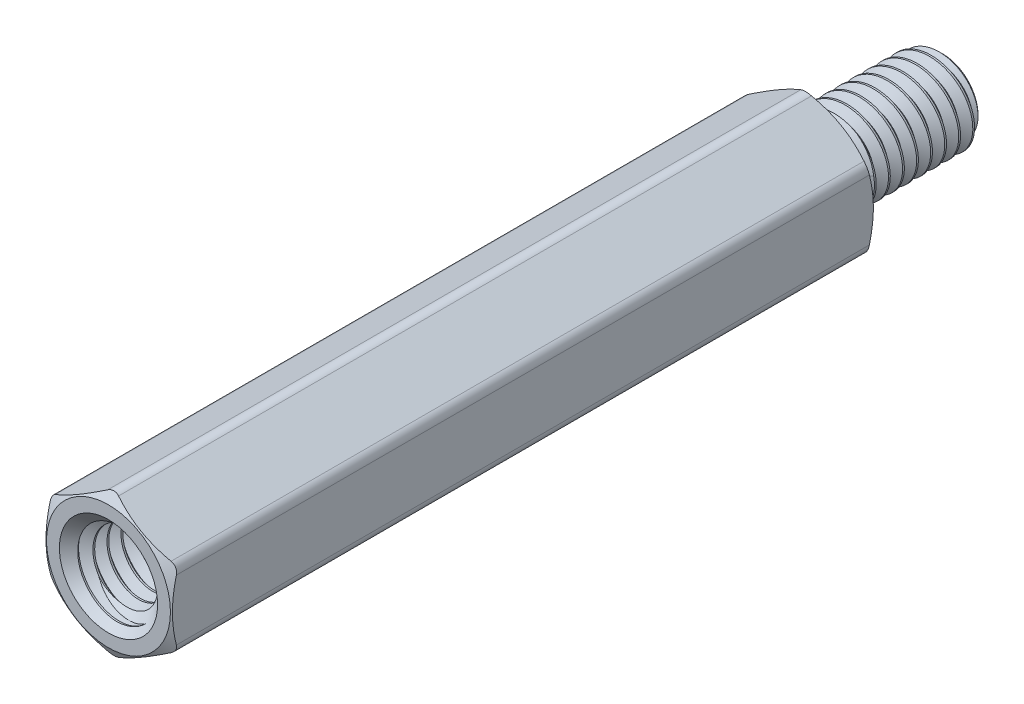
SolidWorks part; units mm, degrees
ref_plane "Front Plane" through (0, 0, 0) normal (0, 0, 1) x (1, 0, 0)
ref_plane "Top Plane" through (0, 0, 0) normal (0, 1, 0) x (1, 0, 0)
ref_plane "Right Plane" through (0, 0, 0) normal (1, 0, 0) x (0, 0, -1)
sketch "Sketch1" plane through (0, 0, 0) normal (0, 0, 1) x (1, 0, 0)
  line L1 (2.25, 1.299) -> (0, 2.5981)
  line L2 (0, 2.5981) -> (-2.25, 1.299)
  line L3 (-2.25, 1.299) -> (-2.25, -1.299)
  line L4 (-2.25, -1.299) -> (0, -2.5981)
  line L5 (0, -2.5981) -> (2.25, -1.299)
  line L6 (2.25, -1.299) -> (2.25, 1.299)
  circle A0 centre (0, 0) radius 2.25 construction
  point P10 (0, -2.25)
  dimension "Hex Size" = 4.5
sketch "Sketch2" plane through (0, 0, 0) normal (1, 0, 0) x (0, 0, -1)
  line L0 (4.7, 0) -> (-25, 0) construction
  line L2 (0, 1.5) -> (0, -1.5) construction
  line L3 (-18.6, 1.5) -> (-18.6, -1.5) construction
  line L4 (-25.4688, 1.5541) -> (-25.2188, 1.1211) construction
  line L5 (-25.2188, 1.1211) -> (-24.9688, 1.5541) construction
  line L6 (-24.9688, 1.5541) -> (-25.4688, 1.5541) construction
  line L7 (-25.4375, 1.5) -> (-25, 1.5) construction
  line L8 (-25.25, 1.1752) -> (-25.1875, 1.1752) construction
  line L9 (-25.2188, 1.1752) -> (-25.2188, 1.1211) construction
  line L10 (-25.2188, 1.5) -> (-25.2188, 1.5541) construction
  line L11 (4.6688, 1.5541) -> (5.1688, 1.5541) construction
  line L12 (5.1688, 1.5541) -> (4.9188, 1.1211) construction
  line L13 (4.9188, 1.1211) -> (4.6688, 1.5541) construction
  line L14 (4.7, 1.5) -> (5.1375, 1.5) construction
  line L15 (4.8875, 1.1752) -> (4.95, 1.1752) construction
  line L16 (4.9188, 1.1752) -> (4.9188, 1.1211) construction
  line L17 (4.9188, 1.5) -> (4.9188, 1.5541) construction
  line L18 (0, 2.5981) -> (-25, 2.5981) construction
  point P6 (0, 0)
  point P9 (-18.6, 0)
  dimension "Length" = 25
sketch "Sketch3" plane through (0, 0, 0) normal (1, 0, 0) x (0, 0, -1)
  line L0 (-18.6, 0) -> (4.7, 0)
  line L1 (-18.6, 1.5) -> (-18.6, -1.5) construction
  line L2 (4.7, 0) -> (4.7, 1.25)
  line L3 (4.7, 1.25) -> (4.45, 1.5)
  line L4 (4.45, 1.5) -> (0.7515, 1.5)
  line L5 (0.7515, 1.5) -> (0.564, 1.1752)
  line L6 (-18.6, 0) -> (-18.6, 1.25)
  line L7 (-18.6, 1.25) -> (-18.85, 1.5)
  line L8 (-18.85, 1.5) -> (-24.75, 1.5)
  line L9 (-24.75, 1.5) -> (-25, 1.75)
  line L10 (4.45, 0) -> (4.45, -1.5) construction
  line L11 (-25, 1.75) -> (-25, 2.25)
  line L12 (-25, 2.25) -> (0, 2.25)
  line L14 (0.564, 1.1752) -> (0.25, 1.1752)
  line L15 (0, 1.4252) -> (0, 2.25)
  arc A0 (0, 1.4252) -> (0.25, 1.1752) centre (0.25, 1.4252) ccw
  point P5 (-25, -2.25)
  point P8 (-23.75, -1.5)
  point P9 (3.45, -1.5)
  point P27 (0, 1.1752)
  dimension "D4" = 0.25
  dimension "D2" = 0.25
  dimension "D1" = 45
  dimension "D6" = 1.25
  dimension "D7" = 60
  dimension "D3" = 1.25
  dimension "D5" = 0.564
revolve "Revolve1" add sketch "Sketch3" angle 360 about L0
sketch "Sketch4" plane through (0, 0, 25) normal (0, 0, 1) x (1, 0, 0)
  line L0 (0, 2.25) -> (0, 1.5) construction
  line L1 (-2.25, 1.299) -> (-2.25, -1.299)
  line L2 (-2.25, -1.299) -> (0, -2.5981)
  line L3 (0, -2.5981) -> (2.25, -1.299)
  line L4 (2.25, -1.299) -> (2.25, 1.299)
  line L5 (2.25, 1.299) -> (0, 2.5981)
  line L6 (0, 2.5981) -> (-2.25, 1.299)
  circle A0 centre (0, 0) radius 2.25 construction
  circle A1 centre (0, 0) radius 1.875
  circle A2 centre (0, 0) radius 2.25 construction
  point P16 (0, 1.875)
extrude "Boss-Extrude1" add sketch "Sketch4" against normal up to surface (25 mm away) up to face at (0, 2.25, 0)
sketch "Sketch5" plane through (0, 0, 25) normal (0, 0, 1) x (1, 0, 0)
  line L0 (-0.8604, 1.2287) -> (0.8604, -1.2287) construction
  line L1 (0, 1.5) -> (0, -1.5) construction
  line L3 (0, -2.7928) -> (0, 2.7928) construction
  circle A0 centre (0, 0) radius 2.205
  point P11 (0.8604, -1.2287)
  dimension "D1" = 4.41
  dimension "D2" = 35
extrude "Cut-Extrude1" cut sketch "Sketch5" against normal through all draft 60 flip side to cut
sketch "Sketch6" plane through (0, 0, 0) normal (0, 0, -1) x (-1, 0, 0)
  circle A0 centre (0, 0) radius 2.205
  circle A1 centre (0, 0) radius 2.205 construction
extrude "Cut-Extrude2" cut sketch "Sketch6" against normal through all draft 60 flip side to cut
fillet "Fillet1" radius 0.3825 6 edges at (0, 2.5981, 12.5) (-2.25, -1.299, 12.5) (0, -2.5981, 12.5) (2.25, -1.299, 12.5) (2.25, 1.299, 12.5) (-2.25, 1.299, 12.5)
sketch "Drawing1" plane through (0, 0, 0) normal (1, 0, 0) x (0, 0, -1)
  line L0 (-25, 1.5) -> (-18.6, 1.5) construction
  line L1 (-18.6, 1.5) -> (-18.6, -1.5) construction
  line L2 (-18.6, -1.5) -> (-25, -1.5) construction
sketch "Sketch7" plane through (0, 0, 0) normal (-1, 0, 0) x (0, 0, 1)
  line L0 (-4.8875, 1.1752) -> (-4.95, 1.1752)
  line L1 (-4.95, 1.1752) -> (-5.1531, 1.5271)
  line L2 (-5.1688, 1.5541) -> (-4.9188, 1.1211) construction
  line L3 (-5.1531, 1.5271) -> (-4.6844, 1.5271)
  line L4 (-4.9188, 1.1211) -> (-4.6688, 1.5541) construction
  line L5 (-4.6844, 1.5271) -> (-4.8875, 1.1752)
  line L6 (-4.9188, 1.5) -> (-4.9188, 1.5541) construction
  point P12 (-4.9188, 1.5271)
sketch "Sketch8" plane through (0, 0, -4.7) normal (0, 0, -1) x (-1, 0, 0)
  circle A0 centre (0, 0) radius 1.5
curve "Helix/Spiral1" pitch 0.5 height 4.559 turns 9.118
sweep "Cut-Sweep1" cut profiles "Sketch7" path "Helix/Spiral1" align with end faces yes
sketch "Sketch9" plane through (0, 0, 18.6) normal (0, 0, 1) x (1, 0, 0)
  circle A0 centre (0, 0) radius 1.75
extrude "Boss-Extrude2" add sketch "Sketch9" along normal up to surface (6.4 mm away) up to face at (0, 1.75, 25)
sketch "Sketch10" plane through (0, 0, 0) normal (1, 0, 0) x (0, 0, -1)
  line L0 (4.7, 0) -> (-25, 0) construction
  line L1 (-18.6, 1.5) -> (-25, 1.5)
  line L2 (-18.6, 1.5) -> (-18.6, 0)
  line L3 (-18.6, 0) -> (-25, 0)
  line L4 (-25, 1.5) -> (-25, 0)
revolve "Revolve2" add sketch "Sketch10" angle 360 about L0
sketch "Sketch11" plane through (0, 0, 25) normal (0, 0, 1) x (1, 0, 0)
  circle A0 centre (0, 0) radius 1.5
  circle A1 centre (0, 0) radius 1.5 construction
sketch "Sketch12" plane through (0, 0, 0) normal (1, 0, 0) x (0, 0, -1)
  line L0 (-25.25, 1.1752) -> (-25.1875, 1.1752)
  line L1 (-25.1875, 1.1752) -> (-24.9844, 1.5271)
  line L2 (-25.2188, 1.1211) -> (-24.9688, 1.5541) construction
  line L3 (-24.9844, 1.5271) -> (-25.4531, 1.5271)
  line L4 (-25.4688, 1.5541) -> (-25.2188, 1.1211) construction
  line L5 (-25.4531, 1.5271) -> (-25.25, 1.1752)
  line L6 (-25.2188, 1.5) -> (-25.2188, 1.5541) construction
  point P12 (-25.2188, 1.5271)
curve "Helix/Spiral2" pitch 0.5 height 6.9 turns 13.8
sweep "Cut-Sweep2" cut profiles "Sketch12" path "Helix/Spiral2" align with end faces yes
combine bodies "Combine1" operation type subtract main body 113 bodies to subtract 114
sketch "Sketch13" plane through (0, 0, 25) normal (0, 0, 1) x (1, 0, 0)
  circle A0 centre (0, 0) radius 1.7475
  dimension "D1" = 3.495
extrude "Cut-Extrude3" cut sketch "Sketch13" against normal through all draft 45
equation "\"Thread Pitch (B)/8@Sketch2\" = \"Thread Pitch (B)@Sketch2\" / 8"
equation "\"Thread Pitch (A)/8@Sketch2\" = \"Thread Pitch (A)@Sketch2\" / 8"
equation "\"D1@Sketch5\"=\"Hex Size@Sketch1\" * .98"
equation "\"D1@Fillet1\"=\"Hex Size@Sketch1\" * .085"
equation "\"D2@Sketch3\"=\"Thread Pitch (A)@Sketch2\" * .5"
equation "\"D4@Sketch3\" = \"D2@Sketch3\""
equation "\"D6@Sketch3\" = \"Thread Pitch (A)@Sketch2\" * 2.5"
equation "\"D3@Helix/Spiral1\" = \"Thread Length (A)@Sketch2\" - \"D5@Sketch3\" * .25"
equation "\"D4@Helix/Spiral1\" = \"Thread Pitch (A)@Sketch2\""
equation "\"D3@Sketch3\" = \"Thread Pitch (B)@Sketch2\" * 2.5"
equation "\"D5@Sketch3\" = \"Thread Length (A)@Sketch2\" * .12"
equation "\"D3@Helix/Spiral2\" = \"Minimum Thread Length (B)@Sketch2\" + \"Thread Pitch (B)@Sketch2\""
equation "\"D4@Helix/Spiral2\" = \"Thread Pitch (B)@Sketch2\""
equation "\"D1@Sketch13\"=(\"Hex Size@Sketch1\"-\"Thread Size (A)@Sketch2\")*.33+\"Thread Size (A)@Sketch2\""
